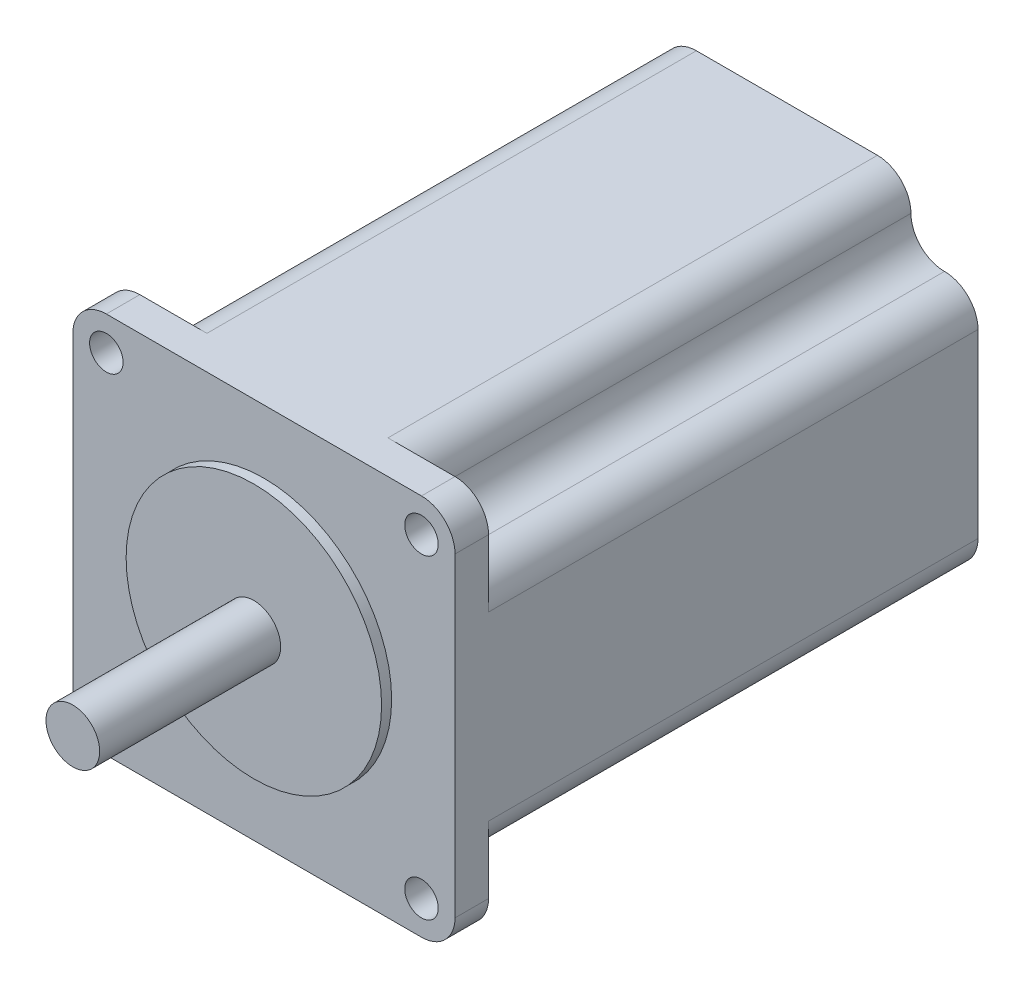
SolidWorks part; units mm, degrees
ref_plane "Front Plane" through (0, 0, 0) normal (0, 0, 1) x (1, 0, 0)
ref_plane "Top Plane" through (0, 0, 0) normal (0, 1, 0) x (1, 0, 0)
ref_plane "Right Plane" through (0, 0, 0) normal (1, 0, 0) x (0, 0, -1)
sketch "Sketch1" plane through (0, 0, 0) normal (0, 0, 1) x (1, 0, 0)
  line L1 (-33.3612, 31.2642) -> (23.6388, 31.2642)
  line L2 (-33.3612, 31.2642) -> (-33.3612, -25.7358)
  line L3 (-33.3612, -25.7358) -> (23.6388, -25.7358)
  line L4 (23.6388, 31.2642) -> (23.6388, -25.7358)
  dimension "D1" = 57
  dimension "D2" = 57
extrude "Boss-Extrude1" add sketch "Sketch1" along normal blind 78
sketch "Sketch2" plane through (0, 0, 0) normal (0, 0, -1) x (-1, 0, 0)
  line L1 (-23.6388, 31.2642) -> (-13.6388, 31.2642)
  line L2 (-23.6388, 31.2642) -> (-23.6388, 21.2642)
  line L3 (-23.6388, 21.2642) -> (-13.6388, 21.2642)
  line L4 (-13.6388, 31.2642) -> (-13.6388, 21.2642)
  dimension "D1" = 10
  dimension "D2" = 10
extrude "Cut-Extrude1" cut sketch "Sketch2" against normal blind 73
pattern_linear "LPattern1" count 2 spacing 47 along (-1, 0, 0) count 2 spacing 47 along (0, -1, 0) of "Cut-Extrude1"
sketch "Sketch3" plane through (0, 0, 78) normal (0, 0, 1) x (1, 0, 0)
  line L0 (23.6388, 31.2642) -> (-33.3612, 31.2642) construction
  line L1 (-33.3612, 31.2642) -> (-33.3612, -25.7358) construction
  circle A0 centre (-28.3612, 26.2642) radius 2.5
  dimension "D3" = 5
  dimension "D1" = 5
  dimension "D2" = 5
extrude "Cut-Extrude2" cut sketch "Sketch3" against normal blind 50
pattern_linear "LPattern2" count 2 spacing 47 along (1, 0, 0) count 2 spacing 47 along (0, -1, 0) of "Cut-Extrude2"
fillet "Fillet1" radius 5 16 edges at (-33.3612, 21.2642, 36.5) (-23.3612, 21.2642, 36.5) (-23.3612, 31.2642, 36.5) (13.6388, 31.2642, 36.5) (13.6388, 21.2642, 36.5) (23.6388, 21.2642, 36.5) (23.6388, -25.7358, 75.5) (23.6388, -15.7358, 36.5) (13.6388, -15.7358, 36.5) (13.6388, -25.7358, 36.5) (-23.3612, -25.7358, 36.5) (-23.3612, -15.7358, 36.5) (-33.3612, -15.7358, 36.5) (-33.3612, -25.7358, 75.5) (-33.3612, 31.2642, 75.5) (23.6388, 31.2642, 75.5)
sketch "Sketch5" plane through (0, 0, 78) normal (0, 0, 1) x (1, 0, 0)
  line L0 (18.6388, 31.2642) -> (-28.3612, 31.2642) construction
  line L1 (-33.3612, 26.2642) -> (-33.3612, -20.7358) construction
  circle A0 centre (-4.8612, 2.7642) radius 19.05
  dimension "D1" = 28.5
  dimension "D2" = 28.5
extrude "Boss-Extrude3" add sketch "Sketch5" along normal blind 1.5
sketch "Sketch4" plane through (0, 0, 78) normal (0, 0, 1) x (1, 0, 0)
  line L0 (18.6388, 31.2642) -> (-28.3612, 31.2642) construction
  line L1 (23.6388, -20.7358) -> (23.6388, 26.2642) construction
  circle A0 centre (-4.8612, 2.7642) radius 4
  dimension "D3" = 8
  dimension "D1" = 28.5
  dimension "D2" = 28.5
extrude "Boss-Extrude2" add sketch "Sketch4" along normal blind 28.5
